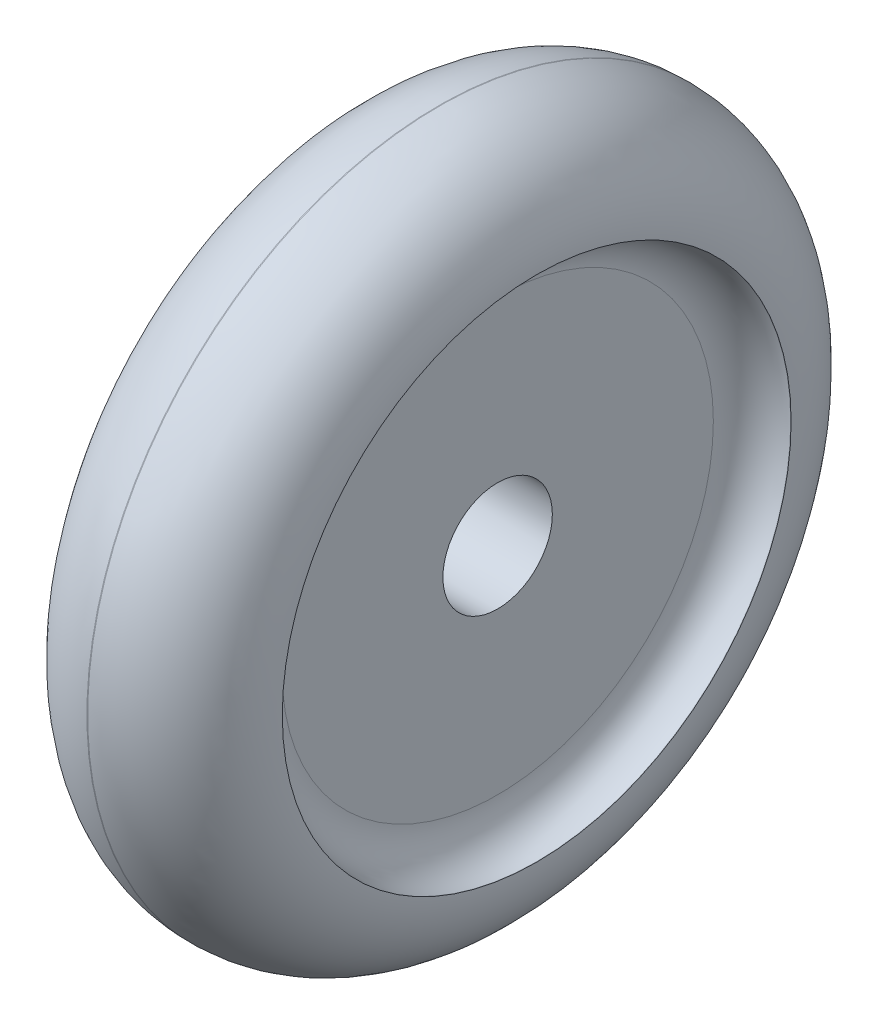
SolidWorks part; units mm, degrees
ref_plane "Front Plane" through (0, 0, 0) normal (0, 0, 1) x (1, 0, 0)
ref_plane "Top Plane" through (0, 0, 0) normal (0, 1, 0) x (1, 0, 0)
ref_plane "Right Plane" through (0, 0, 0) normal (1, 0, 0) x (0, 0, -1)
sketch "Sketch2" plane through (0, 0, 0) normal (1, 0, 0) x (0, 0, -1)
  circle A0 centre (0, 0) radius 9
  dimension "D1" = 18
extrude "Boss-Extrude1" add sketch "Sketch2" along normal blind 5
fillet "Fillet1" radius 2.49 2 edges at (0, 0, -9) (5, 0, -9)
ref_plane "Plane1" through (2.5, 0, 0) normal (1, 0, 0) x (0, 0, -1)
sketch "Sketch3" plane through (5, 0, 0) normal (1, 0, 0) x (0, 0, -1)
  circle A0 centre (0, 0) radius 6.51 construction
  circle A1 centre (0, 0) radius 6.51
extrude "Cut-Extrude1" cut sketch "Sketch3" against normal blind 1
mirror "Mirror1" about plane through (2.5, 0, 0) normal (1, 0, 0) of "Cut-Extrude1"
sketch "Sketch4" plane through (1, 0, 0) normal (-1, 0, 0) x (0, 0, 1)
  circle A0 centre (0, 0) radius 1.4
  dimension "D1" = 2.8
extrude "Cut-Extrude2" cut sketch "Sketch4" against normal through all
fillet "Fillet2" radius 0.99 2 edges at (4, 0, -6.51) (1, 0, -6.51)
